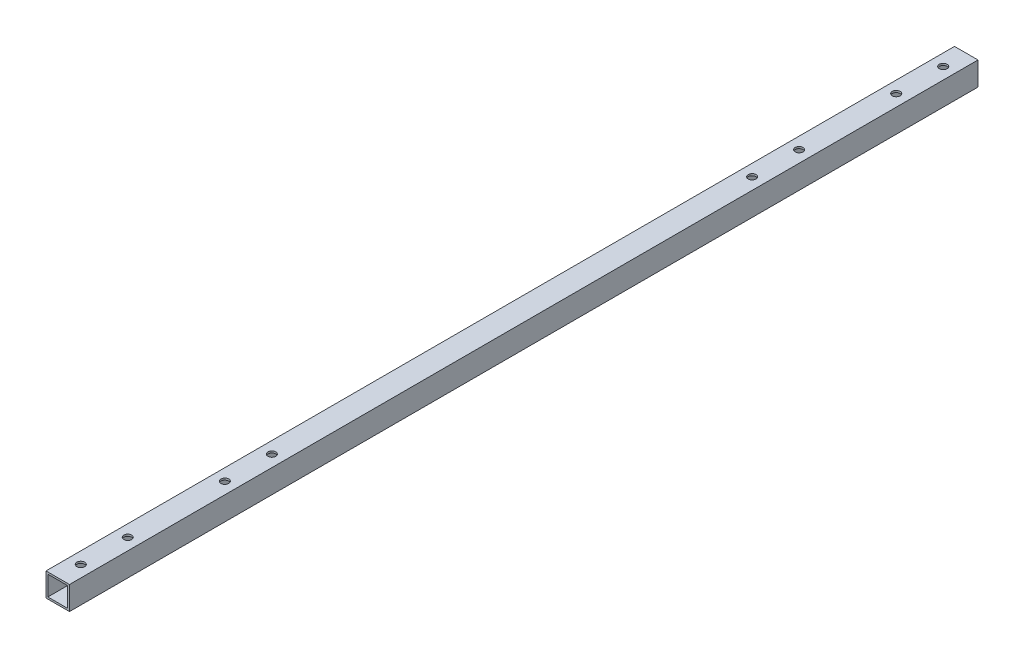
SolidWorks part; units mm, degrees
material "7050-T73510"
ref_plane "Front" through (0, 0, 0) normal (0, 0, 1) x (1, 0, 0)
ref_plane "Top" through (0, 0, 0) normal (0, 1, 0) x (1, 0, 0)
ref_plane "Right" through (0, 0, 0) normal (1, 0, 0) x (0, 0, -1)
sketch "草图1" plane through (0, 0, 0) normal (0, 0, 1) x (1, 0, 0)
  line L0 (-6.3, -6.3) -> (-6.3, 6.3)
  line L1 (-7.5, -7.5) -> (7.5, -7.5)
  line L2 (-7.5, -7.5) -> (-7.5, 7.5)
  line L3 (-7.5, 7.5) -> (7.5, 7.5)
  line L4 (7.5, -7.5) -> (7.5, 7.5)
  line L5 (-7.5, -7.5) -> (7.5, 7.5) construction
  line L6 (-7.5, 7.5) -> (7.5, -7.5) construction
  line L7 (-6.3, 6.3) -> (6.3, 6.3)
  line L8 (6.3, -6.3) -> (6.3, 6.3)
  line L9 (-6.3, -6.3) -> (6.3, -6.3)
  point P0 (0, 0)
  dimension "D1" = 15
  dimension "D2" = 15
  dimension "D3" = 1.2
extrude "凸台-拉伸1" add sketch "草图1" along normal blind 570
sketch "草图4" plane through (0, 0, 570) normal (0, 0, 1) x (1, 0, 0)
  line L0 (6.3, 6.3) -> (-6.3, 6.3) construction
  line L1 (6.3, -6.3) -> (6.3, 6.3) construction
  line L2 (-6.3, -6.3) -> (6.3, -6.3) construction
  line L3 (6.3, 6.3) -> (-6.3, 6.3)
  line L4 (7.5, -7.5) -> (7.5, 7.5)
  line L5 (7.5, 7.5) -> (-7.5, 7.5)
  line L6 (-7.5, 7.5) -> (-7.5, -7.5)
  line L7 (-7.5, -7.5) -> (7.5, -7.5)
  line L8 (7.5, -7.5) -> (7.5, 7.5)
  line L9 (7.5, 7.5) -> (-7.5, 7.5)
  line L10 (-7.5, 7.5) -> (-7.5, -7.5)
  line L11 (-7.5, -7.5) -> (7.5, -7.5)
  line L12 (6.3, -6.3) -> (6.3, 6.3)
  line L13 (-6.3, -6.3) -> (6.3, -6.3)
  line M9 (6.3, -6.3) -> (-6.3, -6.3)
  line M10 (-6.3, -6.3) -> (-6.3, 6.3)
  line M11 (-6.3, 6.3) -> (6.3, 6.3)
  line M12 (6.3, 6.3) -> (6.3, -6.3)
  dimension "D1" = 0
extrude "凸台-拉伸2" add sketch "草图4" along normal blind 10 contours M9 M12 M11 M10 | L10 L11 L8 L9 region at (0, 0, 570)
sketch "草图2" plane through (0, -7.5, 0) normal (0, -1, 0) x (1, 0, 0)
  circle A4 centre (0, 565.3031) radius 2.5
  circle A5 centre (0, 535.3031) radius 2.5
  circle A6 centre (0, 473.3031) radius 2.5
  circle A7 centre (0, 443.3031) radius 2.5
extrude "切除-拉伸1" cut sketch "草图2" against normal blind 25
ref_plane "基准面1" through (0, 0, 290) normal (0, 0, 1) x (1, 0, 0)
mirror "镜向1" about plane through (0, 0, 290) normal (0, 0, 1) of "切除-拉伸1"
